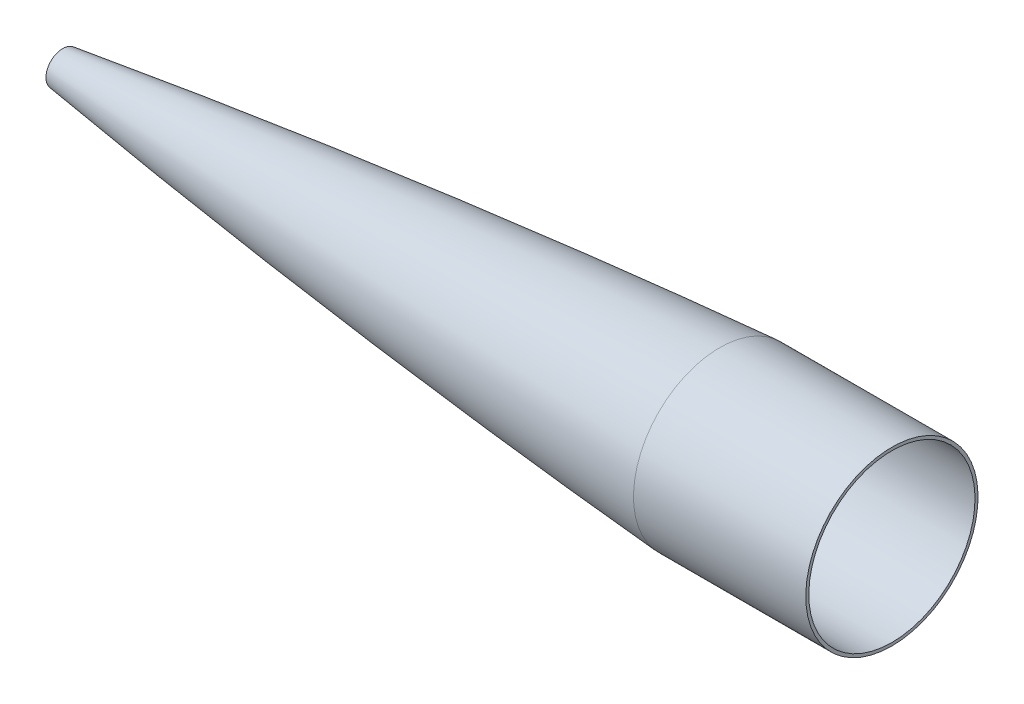
SolidWorks part; units mm, degrees
material "PVC 0.007 Plasticized"
ref_plane "Płaszczyzna przednia" through (0, 0, 0) normal (0, 0, 1) x (1, 0, 0)
ref_plane "Płaszczyzna górna" through (0, 0, 0) normal (0, 1, 0) x (1, 0, 0)
ref_plane "Płaszczyzna prawa" through (0, 0, 0) normal (1, 0, 0) x (0, 0, -1)
ref_plane "Plane1" through (0, 0, 0) normal (0, 0, -1) x (-1, 0, 0)
sketch "Sketch1" plane through (0, 0, 0) normal (0, 0, -1) x (-1, 0, 0)
  line L2 (-763.2353, 0) -> (0, 0) construction
  line L8 (-763.3824, 85) -> (-763.2353, 85)
  line L13 (-763.3824, 82) -> (-763.3458, 82)
  line L14 (-763.3824, 85) -> (-763.3824, 82)
  line L15 (0, 0) -> (-22.4653, 0)
  line L16 (-22.4653, 0) -> (-22.4653, 0.2965)
  arc A0 (0, 0) -> (-763.2353, 85) centre (-1520.6726, -10185.346) ccw
  arc A4 (-22.4653, 0.2965) -> (-763.3458, 82) centre (-1520.6726, -10185.346) ccw
  arc A5 (-0.443, -2.9671) -> (-763.3458, 82) centre (-1520.6726, -10185.346) ccw construction
  dimension "D1" = 85
  dimension "D2" = 3
revolve "Revolve1" add sketch "Sketch1" angle 360 about L2 reverse direction yes
sketch "Sketch14" plane through (0, 0, 0) normal (0, 0, -1) x (-1, 0, 0)
  line L1 (-763.2353, 0) -> (-933.2353, 0) construction
  line L2 (-933.2353, 0) -> (-933.2353, 85) construction
  line L12 (-763.3824, 85) -> (-933.2353, 85)
  line L13 (-763.3824, 85) -> (-763.2353, 82)
  line L14 (-763.2353, 82) -> (-933.2353, 82)
  line L15 (-933.2353, 82) -> (-933.2353, 85)
  dimension "D1" = 3
revolve "Revolve4" add sketch "Sketch14" angle 360 about L1
sketch "Sketch16" plane through (0, 0, 0) normal (0, 0, 1) x (1, 0, 0)
  line L18 (763.1248, 88) -> (753.3824, 77.2491)
  line L20 (97.5171, 0) -> (789.3389, 0) construction
  line L24 (107.5171, 8.4062) -> (107.5171, 18.5017)
  line L25 (763.2353, 85) -> (933.2353, 85)
  line L27 (933.2353, 85) -> (933.2353, -85)
  line L28 (763.2353, 85) -> (933.2353, 85)
  line L29 (933.2353, 85) -> (933.2353, -85)
  line L30 (933.2353, -85) -> (763.2353, -85)
  line L31 (933.2353, -85) -> (763.2353, -85)
  arc A4 (753.3824, 77.2491) -> (107.5171, 8.4062) centre (1520.6726, -10185.346) ccw
  arc A9 (0, 0) -> (763.2353, -85) centre (1520.6726, 10185.346) ccw
  arc A10 (763.2353, 85) -> (0, 0) centre (1520.6726, -10185.346) ccw
  arc A11 (0, 0) -> (763.2353, -85) centre (1520.6726, 10185.346) ccw
  arc A12 (763.2353, 85) -> (0, 0) centre (1520.6726, -10185.346) ccw
sketch "Sketch18" plane through (0, 0, 0) normal (0, 0, 1) x (1, 0, 0)
  line L2 (-14.4563, 18.5017) -> (-14.4563, -44.1703)
  line L9 (0, 0) -> (115, 0)
  line L10 (115, 0) -> (115, 28.1932)
  line L11 (115, 28.1932) -> (-14.4563, 28.1932)
  line L12 (-14.4563, 28.1932) -> (-14.4563, 18.5017)
  line L13 (-14.4563, -44.1703) -> (115, -44.1703)
  line L14 (115, -44.1703) -> (115, 0)
extrude "Cut-Extrude3" cut sketch "Sketch18" against normal mid plane 500 contours L13 L14 L10 L11 L12 L2 region at (50.2718, -7.9886, 0)
sketch "Sketch19" plane through (0, 0, 0) normal (0, 0, 1) x (1, 0, 0)
  line L0 (115, 16.5069) -> (115, 0)
  line L1 (115, 16.5069) -> (115, -16.5069) construction
  line L2 (115, 0) -> (124.8, 0)
  line L3 (115, 16.5069) -> (124.8, 17.5054)
  line L4 (124.8, 17.5054) -> (124.8, 0)
revolve "Revolve6" add sketch "Sketch19" angle 360 about L2
sketch "Sketch20" plane through (115, 0, 0) normal (-1, 0, 0) x (0, 0, 1)
  circle A0 centre (0, 0) radius 3
  dimension "D1" = 6
extrude "Cut-Extrude4" cut sketch "Sketch20" against normal mid plane 500
sketch "Sketch21" plane through (0, 0, 0) normal (0, 0, 1) x (1, 0, 0)
  line L0 (115, -16.5069) -> (115, 16.5069)
  line L2 (763.2353, 85) -> (933.2353, 85)
  line L4 (933.2353, 85) -> (933.2353, -85)
  line L6 (933.2353, -85) -> (763.2353, -85)
  line L12 (763.2353, 85) -> (933.2353, 85) construction
  line L13 (763.6036, 75) -> (923.2353, 75) construction
  line L14 (923.2353, 75) -> (923.2353, -75) construction
  line L15 (933.2353, 85) -> (933.2353, -85) construction
  line L16 (923.2353, -75) -> (763.6036, -75) construction
  line L17 (933.2353, -85) -> (763.2353, -85) construction
  line L18 (125, -7.7866) -> (125, 7.7866) construction
  line L19 (115, -16.5069) -> (115, 16.5069) construction
  line L20 (115, 0) -> (776.9072, 0) construction
  line L21 (763.2353, 85) -> (763.6036, 75)
  line L22 (125, 7.7866) -> (115, 7.0442)
  line L23 (115, 16.5069) -> (115, -16.5069) construction
  line L24 (115, 16.5069) -> (115, 7.0442)
  arc A0 (763.2353, 85) -> (115, 16.5069) centre (1520.6726, -10185.346) ccw
  arc A1 (763.2353, 85) -> (115, 16.5069) centre (1520.6726, -10185.346) ccw
  arc A2 (115, -16.5069) -> (763.2353, -85) centre (1520.6726, 10185.346) ccw
  arc A4 (763.6036, 75) -> (125, 7.7866) centre (1520.6726, -10185.346) ccw
  arc A6 (125, -7.7866) -> (763.6036, -75) centre (1520.6726, 10185.346) ccw construction
  arc A7 (115, -16.5069) -> (763.2353, -85) centre (1520.6726, 10185.346) ccw construction
  dimension "D1" = 10
revolve "Revolve7" add sketch "Sketch21" angle 5 about L20
pattern_circular "CirPattern2" count 14 over 360 of "Revolve7"
